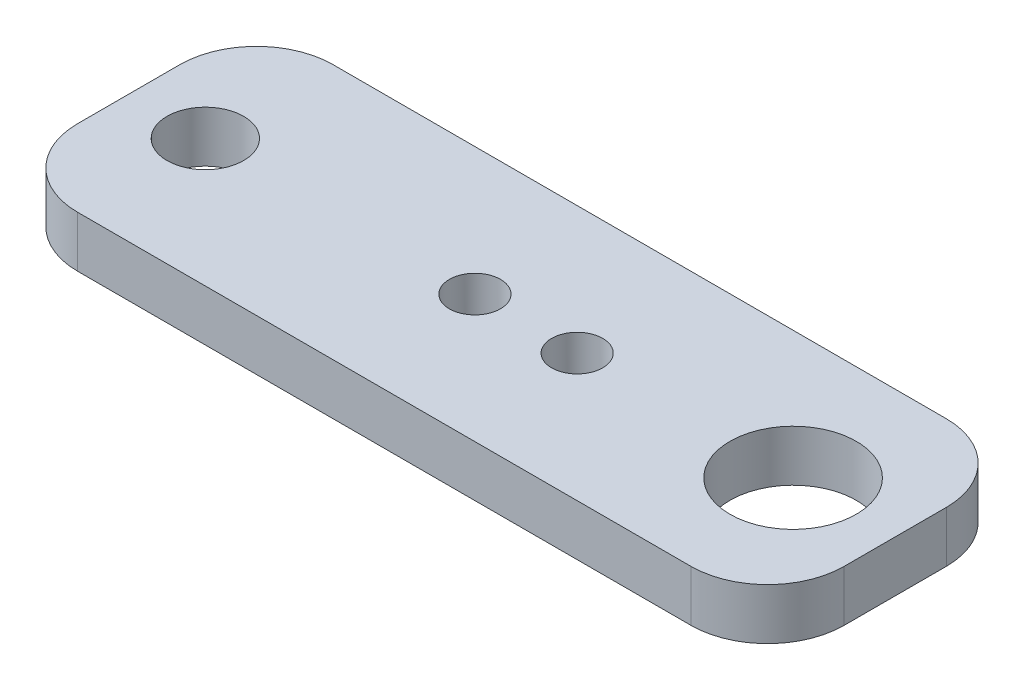
SolidWorks part; units mm, degrees
ref_plane "Front Plane" through (0, 0, 0) normal (0, 0, 1) x (1, 0, 0)
ref_plane "Top Plane" through (0, 0, 0) normal (0, 1, 0) x (1, 0, 0)
ref_plane "Right Plane" through (0, 0, 0) normal (1, 0, 0) x (0, 0, -1)
sketch "Sketch1" plane through (0, 0, 0) normal (0, 1, 0) x (1, 0, 0)
  line L1 (-15, 5) -> (15, 5)
  line L2 (-15, 5) -> (-15, -5)
  line L3 (-15, -5) -> (15, -5)
  line L4 (15, 5) -> (15, -5)
  line L5 (-15, 5) -> (15, -5) construction
  line L6 (-15, -5) -> (15, 5) construction
  point P0 (0, 0)
  dimension "D1" = 10
  dimension "D2" = 30
extrude "Boss-Extrude1" add sketch "Sketch1" along normal blind 2
sketch "Sketch2" plane through (0, 2, 0) normal (0, 1, 0) x (1, 0, 0)
  line L0 (11, 5) -> (11, -5) construction
  line L1 (-15, -5) -> (15, -5) construction
  line L2 (15, -5) -> (15, 5) construction
  circle A0 centre (11, 0) radius 2.4729
  circle A3 centre (2.55, 0) radius 1
  circle A4 centre (-1.45, 0) radius 1
  point P4 (15.0307, 0)
  point P5 (4.6832, 0)
  point P10 (11, 0)
  point P15 (0, 0)
  dimension "D1" = 8.45
  dimension "D4" = 2
  dimension "D2" = 4
  dimension "D3" = 4
extrude "Cut-Extrude1" cut sketch "Sketch2" against normal blind 3
fillet "Fillet1" radius 3 4 edges at (15, 1, 5) (15, 1, -5) (-15, 1, -5) (-15, 1, 5)
hole_wizard "Ø3.0 (3) Diameter Hole1" positions "Sketch3" profile "Sketch4" hole size "Ø3.0" standard "BSI" end condition through all
sketch "Sketch3" plane through (0, 2, 0) normal (0, 1, 0) x (1, 0, 0)
  circle A0 centre (11, 0) radius 2.4729 construction
  point P0 (-12, 0)
  dimension "D1" = 23
sketch "Sketch4" plane through (-12, 2, 0) normal (1, 0, 0) x (0, 0, 1)
  line L0 (0, 0) -> (0, 2)
  line L1 (0, 2) -> (1.5, 2)
  line L2 (1.5, 2) -> (1.5, 0)
  line L5 (1.5, 0) -> (0, 0)
  line L11 (0, -6.35) -> (0, 107.95) construction
  dimension "Thru Hole Dia." = 3
  dimension "Thru Hole Depth" = 2
